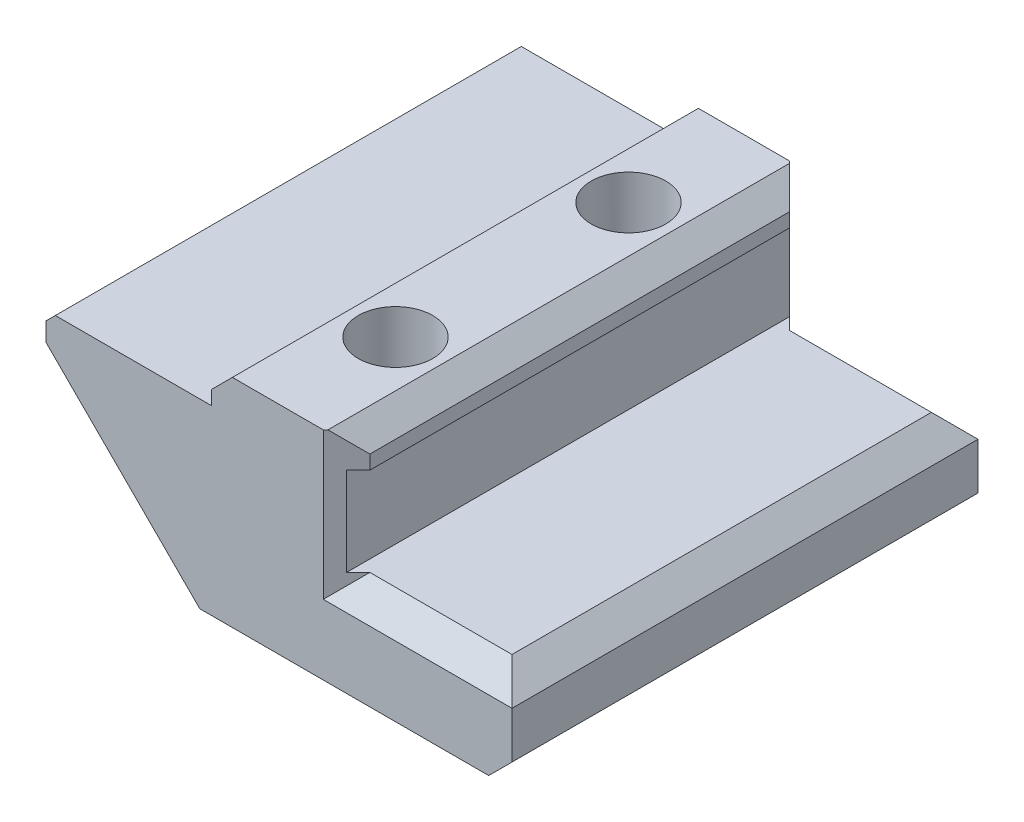
SolidWorks part; units mm, degrees
ref_plane "前视基准面" through (0, 0, 0) normal (0, 0, 1) x (1, 0, 0)
ref_plane "上视基准面" through (0, 0, 0) normal (0, 1, 0) x (1, 0, 0)
ref_plane "右视基准面" through (0, 0, 0) normal (1, 0, 0) x (0, 0, -1)
other "Configuration Table"
sketch "草图1" plane through (0, 0, 0) normal (0, 1, 0) x (1, 0, 0)
  line L1 (0, 0) -> (20, 0)
  line L2 (0, 0) -> (0, 20)
  line L3 (0, 20) -> (20, 20)
  line L4 (20, 0) -> (20, 20)
  dimension "D1" = 20
  dimension "D2" = 20
extrude "凸台-拉伸1" add sketch "草图1" along normal blind 4
sketch "草图2" plane through (0, 4, 0) normal (0, 1, 0) x (1, 0, 0)
  line L0 (0, 0) -> (20, 0) construction
  line L1 (0, 20) -> (12.9, 20)
  line L2 (0, 20) -> (0, 0)
  line L3 (0, 0) -> (12.9, 0)
  line L4 (12.9, 20) -> (12.9, 0)
  line L5 (20, 0) -> (20, 20) construction
  dimension "D1" = 7.1
extrude "凸台-拉伸2" add sketch "草图2" along normal blind 3.8
sketch "草图3" plane through (0, 0, 0) normal (0, -1, 0) x (-1, 0, 0)
  line L0 (0, 20) -> (0, 0) construction
  line L2 (0, 0) -> (-20, 0) construction
  circle A0 centre (-10, 5) radius 1.6
  circle A1 centre (-10, 15) radius 1.6
  dimension "D1" = 3.2
  dimension "D3" = 5
  dimension "D2" = 10
  dimension "D4" = 2
extrude "切除-拉伸1" cut sketch "草图3" against normal through all
sketch "草图4" plane through (0, 7.8, 0) normal (0, 1, 0) x (1, 0, 0)
  line L0 (12.9, 20) -> (0, 20) construction
  line L1 (7.1, 20) -> (12.9, 20)
  line L2 (7.1, 20) -> (7.1, 0)
  line L3 (7.1, 0) -> (12.9, 0)
  line L4 (12.9, 20) -> (12.9, 0)
  line L5 (0, 20) -> (0, 0) construction
  circle A0 centre (10, 15) radius 1.6
  circle A1 centre (10, 5) radius 1.6
  point P6 (10, 20)
  dimension "D1" = 5.8
  dimension "D2" = 10
extrude "凸台-拉伸3" add sketch "草图4" along normal blind 1.5
sketch "草图5" plane through (0, 0, 0) normal (0, -1, 0) x (-1, 0, 0)
  circle A0 centre (-10, 5) radius 3
  circle A1 centre (-10, 15) radius 3
  dimension "D1" = 6
  dimension "D2" = 6
extrude "切除-拉伸3" cut sketch "草图5" against normal blind 2.4
chamfer "倒角3" distance 1.5 angle 45 2 edges at (10, 2.4, -16.6) (10, 2.4, -6.6)
chamfer "倒角1" distance 6.6 angle 45 1 edges at (0, 0, -10)
chamfer "倒角2" distance 1 angle 45 6 edges at (20, 0, -10) (12.9, 6.65, -20) (16.45, 4, -20) (20, 4, -10) (16.45, 4, 0) (12.9, 6.65, 0)
chamfer "倒角4" distance 0.4 angle 45 1 edges at (0, 7.8, -10)
chamfer "倒角5" distance 0.9 angle 45 2 edges at (12.9, 9.3, -10) (7.1, 9.3, -10)
sketch "草图7" plane through (12.9, 0, 0) normal (1, 0, 0) x (0, 0, -1)
  line L1 (20, 7.8) -> (-1.0616, 7.8)
  line L2 (20, 7.8) -> (20, 4)
  line L3 (20, 4) -> (-1.0616, 4)
  line L4 (-1.0616, 7.8) -> (-1.0616, 4)
extrude "切除-拉伸6" cut sketch "草图7" against normal blind 0.5
